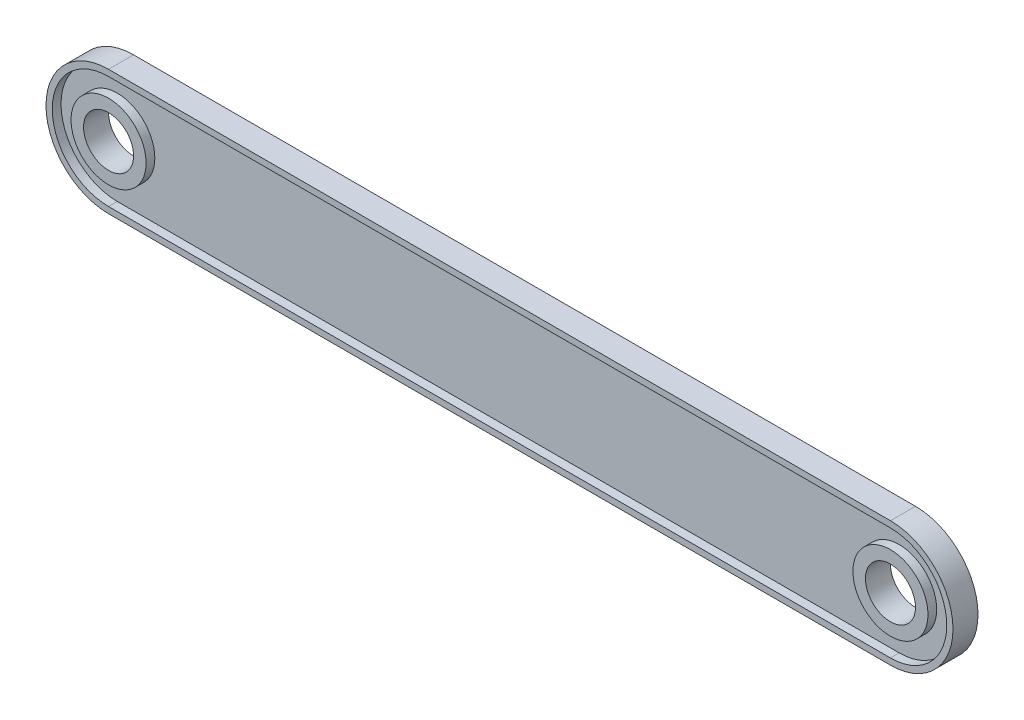
SolidWorks part; units mm, degrees
ref_plane "Front Plane" through (0, 0, 0) normal (0, 0, 1) x (1, 0, 0)
ref_plane "Top Plane" through (0, 0, 0) normal (0, 1, 0) x (1, 0, 0)
ref_plane "Right Plane" through (0, 0, 0) normal (1, 0, 0) x (0, 0, -1)
sketch "Sketch1" plane through (0, 0, 0) normal (0, 0, 1) x (1, 0, 0)
  line L0 (0, 0) -> (625, 0) construction
  line L1 (0, 50) -> (625, 50)
  line L2 (0, -50) -> (625, -50)
  line L3 (0, 45) -> (625, 45)
  line L4 (0, -45) -> (625, -45)
  arc A0 (0, 50) -> (0, -50) centre (0, 0) ccw
  arc A1 (625, -50) -> (625, 50) centre (625, 0) ccw
  arc A2 (625, -45) -> (625, 45) centre (625, 0) ccw
  arc A3 (0, 45) -> (0, -45) centre (0, 0) ccw
  circle A4 centre (0, 0) radius 30
  circle A5 centre (0, 0) radius 20
  circle A6 centre (625, 0) radius 30
  circle A7 centre (625, 0) radius 20
  point P3 (312.5, 0)
  dimension "D4" = 40
  dimension "D5" = 10
  dimension "D1" = 625
  dimension "D2" = 100
  dimension "D3" = 5
extrude "Boss-Extrude1" add sketch "Sketch1" along normal mid plane 6 contours L3 A3 L4 A2 A4 A6 region at (312.5, 0, 0)
extrude "Boss-Extrude2" add sketch "Sketch1<3>" along normal mid plane 20 contours L2 A1 L1 A0 A3 L3 A2 L4 | A5 A4 | A6 A7 region at (312.5, 49.2681, 0) region at (-29.1515, 0, 0) region at (595.8485, 0, 0)
sketch "Sketch1<3>" plane through (0, 0, 0) normal (0, 0, 1) x (1, 0, 0) same geometry as "Sketch1"
